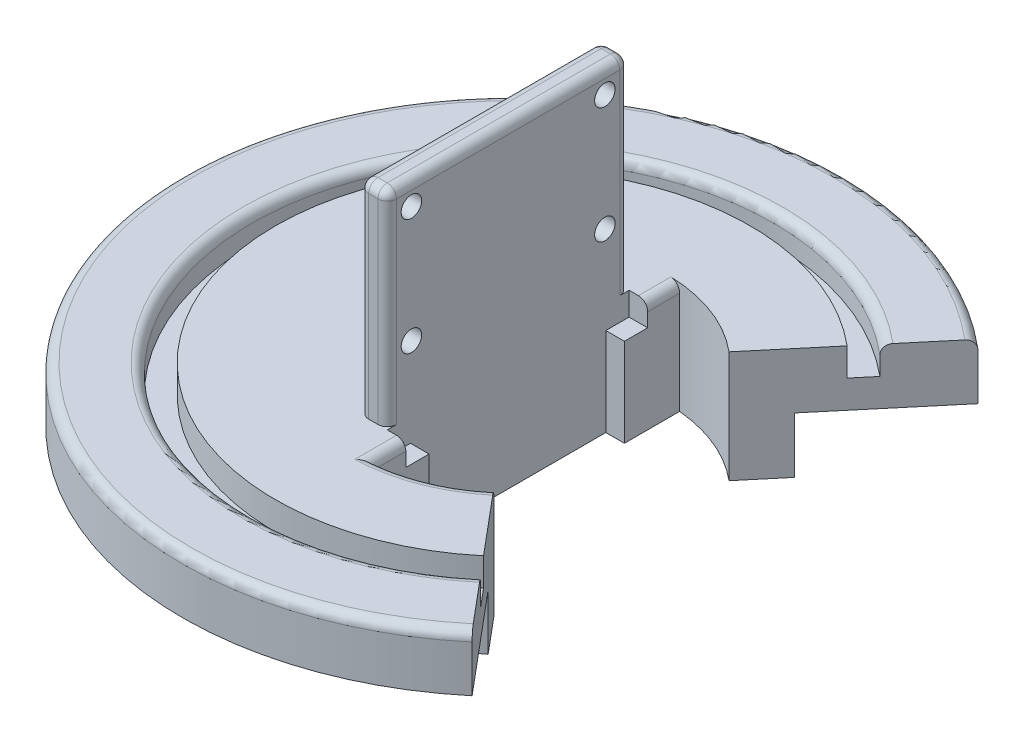
SolidWorks part; units mm, degrees
material "ABS"
ref_plane "Plano frontal" through (0, 0, 0) normal (0, 0, 1) x (1, 0, 0)
ref_plane "Plano superior" through (0, 0, 0) normal (0, 1, 0) x (1, 0, 0)
ref_plane "Plano direito" through (0, 0, 0) normal (1, 0, 0) x (0, 0, -1)
sketch "Esboço1" plane through (0, 0, 0) normal (0, 1, 0) x (1, 0, 0)
  line L0 (0, 0) -> (0, 19.2443) construction
  line L1 (0, 0) -> (-21.0937, 0) construction
  line L2 (1.5, -16.4317) -> (1.5, -13)
  line L3 (-0.5, -13) -> (1.5, -13)
  line L4 (-0.5, -13) -> (-0.5, 13)
  line L5 (-0.5, 13) -> (1.5, 13)
  line L6 (0, 0) -> (13.8199, -16.47) construction
  line L7 (1.5, 16.4317) -> (1.5, 13)
  line L8 (0, 0) -> (13.8199, 16.47) construction
  line L9 (13.8199, -16.47) -> (10.606, -12.6397)
  line L10 (13.8199, 16.47) -> (10.606, 12.6397)
  arc A0 (13.8199, 16.47) -> (13.8199, -16.47) centre (0, 0) ccw
  arc A2 (10.606, 12.6397) -> (1.5, 16.4317) centre (0, 0) ccw
  arc A3 (1.5, -16.4317) -> (10.606, -12.6397) centre (0, 0) ccw
  dimension "D1" = 2
  dimension "D6" = 100
  dimension "D4" = 5
  dimension "D5" = 43
  dimension "D2" = 0.5
  dimension "D3" = 26
extrude "Ressalto-extrusão1" add sketch "Esboço1" against normal blind 12
sketch "Esboço3" plane through (0, 0, 0) normal (0, 1, 0) x (1, 0, 0)
  line L0 (13.8199, -16.47) -> (22.819, -27.1946)
  line L1 (13.8199, 16.47) -> (22.819, 27.1946)
  arc A0 (22.819, 27.1946) -> (22.819, -27.1946) centre (0, 0) ccw
  circle A1 centre (0, 0) radius 21.5 construction
  arc A2 (13.8199, 16.47) -> (13.8199, -16.47) centre (0, 0) ccw
  dimension "D1" = 14
extrude "Ressalto-extrusão3" add sketch "Esboço3" against normal blind 6
sketch "Esboço4" plane through (0, 0, 0) normal (0, 1, 0) x (1, 0, 0)
  line L2 (-0.5, -13) -> (-0.5, 13)
  line L3 (-0.5, -13) -> (-3.5, -13)
  line L4 (-0.5, 13) -> (-3.5, 13)
  line L5 (-3.5, -13) -> (-3.5, 13)
  dimension "D1" = 3
extrude "Ressalto-extrusão4" add sketch "Esboço4" along normal blind 22
sketch "Esboço6" plane through (-0.5, 0, 0) normal (1, 0, 0) x (0, 0, -1)
  line L0 (13, -12) -> (-13, -12) construction
  line L1 (-13, -2.5) -> (-10.5, -2.5)
  line L2 (-13, -2.5) -> (-13, -12)
  line L3 (-13, -12) -> (-10.5, -12)
  line L4 (-10.5, -2.5) -> (-10.5, -12)
  line L5 (0, 0) -> (0, -6.7935) construction
  line L6 (13, -2.5) -> (10.5, -2.5)
  line L7 (13, -2.5) -> (13, -12)
  line L8 (13, -12) -> (10.5, -12)
  line L9 (10.5, -2.5) -> (10.5, -12)
  line L11 (13, 0) -> (-13, 0) construction
  line L12 (-13, -12) -> (-13, 0) construction
  line L13 (13, -12) -> (13, 0) construction
  point P15 (0, 0)
  dimension "D1" = 2.5
  dimension "D2" = 2.5
extrude "Ressalto-extrusão5" add sketch "Esboço6" along normal up to surface (2 mm away) up to face at (1.5, -6, 14.7158)
sketch "Esboço7" plane through (-0.5, 0, 0) normal (1, 0, 0) x (0, 0, -1)
  line L0 (0, 22) -> (0, 0) construction
  line L1 (-13, 22) -> (13, 22) construction
  line L2 (35.5, 0) -> (-35.5, 0) construction
  line L3 (13, -2.5) -> (10.5, -2.5) construction
  circle A0 centre (-10.4, 19.5) radius 1.1
  circle A1 centre (10.4, 19.5) radius 1.1
  circle A2 centre (10.4, 7) radius 1.1
  circle A3 centre (-10.4, 7) radius 1.1
  dimension "D1" = 2.2
  dimension "D2" = 9.5
  dimension "D3" = 12.5
  dimension "D4" = 20.8
extrude "Corte-extrusão1" cut sketch "Esboço7" against normal through all
sketch "Esboço8" plane through (0, 0, 0) normal (0, 1, 0) x (1, 0, 0)
  circle A0 centre (0, 0) radius 28.0141
  circle A1 centre (0, 0) radius 25.5141
  circle A2 centre (0, 0) radius 28.0141 construction
  dimension "D1" = 2.5
extrude "Corte-extrusão2" cut sketch "Esboço8" against normal blind 3
fillet "Filete1" radius 1 12 edges at (1.5, 0, -14.7158) (-28.0141, 0, 0) (1.5, 0, 14.7158) (-35.5, 0, 0) (-3.5, 11, 13) (-0.5, 11, 13) (-0.5, 11, -13) (-3.5, 11, -13) (-2, 22, 13) (-0.5, 22, 0) (-2, 22, -13) (-3.5, 22, 0)
